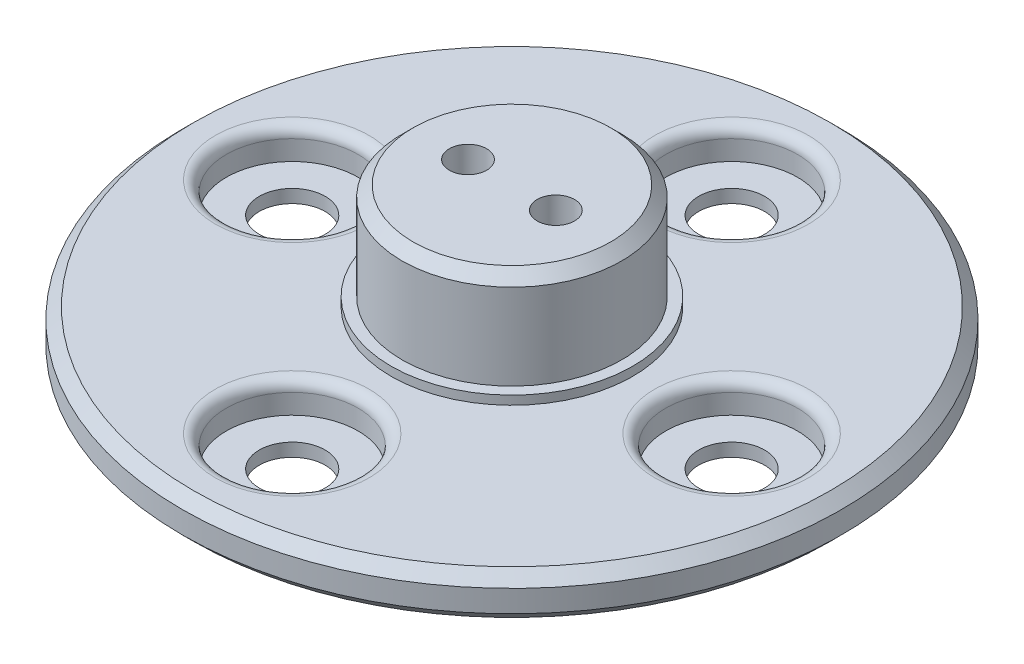
SolidWorks part; units mm, degrees
ref_plane "前视基准面" through (0, 0, 0) normal (0, 0, 1) x (1, 0, 0)
ref_plane "上视基准面" through (0, 0, 0) normal (0, 1, 0) x (1, 0, 0)
ref_plane "右视基准面" through (0, 0, 0) normal (1, 0, 0) x (0, 0, -1)
other "Configuration Table"
sketch "草图1" plane through (0, 0, 0) normal (0, 1, 0) x (1, 0, 0)
  line L0 (-21.98, 0) -> (22.6908, 0) construction
  line L1 (0, 22.7485) -> (0, -21.9381) construction
  circle A0 centre (0, 0) radius 15
  circle A1 centre (0, 10) radius 1.5
  circle A2 centre (10, 0) radius 1.5
  circle A3 centre (0, -10) radius 1.5
  circle A4 centre (-10, 0) radius 1.5
  point P15 (0, 0)
  dimension "D1" = 3
  dimension "D3" = 30
  dimension "D2" = 10
extrude "凸台-拉伸1" add sketch "草图1" along normal blind 2
sketch "草图2" plane through (0, 2, 0) normal (0, 1, 0) x (1, 0, 0)
  line L0 (0, 1.9211) -> (0, -1.7964) construction
  line L1 (-1.959, 0) -> (1.7076, 0) construction
  circle A1 centre (0, 0) radius 5
  circle A3 centre (2, 0) radius 0.85
  circle A4 centre (-2, 0) radius 0.85
  dimension "D1" = 10
  dimension "D2" = 1.7
  dimension "D3" = 4
extrude "凸台-拉伸2" add sketch "草图2" along normal blind 4.8
sketch "草图4" plane through (0, 2, 0) normal (0, 1, 0) x (1, 0, 0)
  circle A8 centre (0, 0) radius 5.5
  point P15 (0, 0)
  dimension "D1" = 11
extrude "凸台-拉伸3" add sketch "草图4" along normal blind 0.4
chamfer "倒角1" distance 0.5 angle 45 1 edges at (0, 6.8, 5)
chamfer "倒角3" distance 0.5 angle 45 2 edges at (0, 0, 15) (0, 2, 15)
sketch "草图5" plane through (0, 2, 0) normal (0, 1, 0) x (1, 0, 0)
  circle A0 centre (0, 10) radius 3
  circle A1 centre (10, 0) radius 3
  circle A2 centre (0, -10) radius 3
  circle A3 centre (-10, 0) radius 3
  point P12 (0, 0)
  dimension "D1" = 6
  dimension "D2" = 4
extrude "切除-拉伸1" cut sketch "草图5" against normal blind 1.4
fillet "圆角1" radius 0.5 4 edges at (0, 2, 13) (10, 2, 3) (0, 2, -7) (-10, 2, 3)
